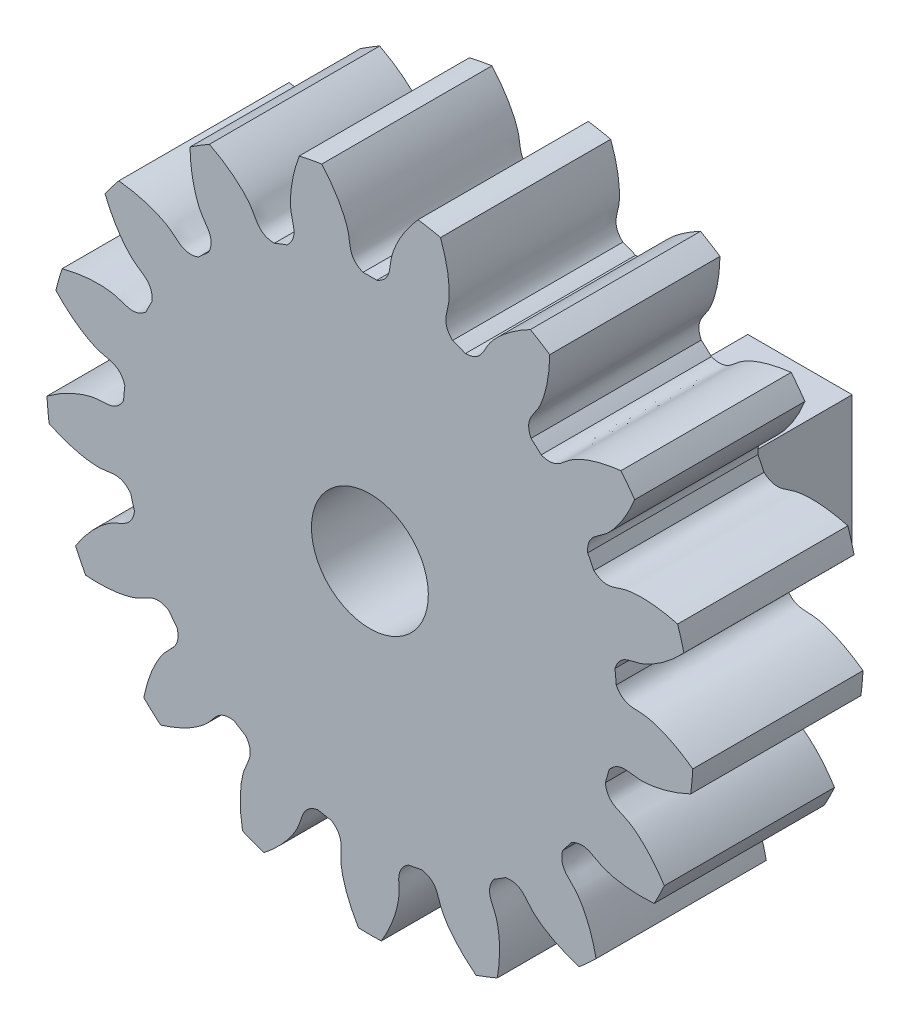
SolidWorks part; units mm, degrees
material "POM 乙缩醛共聚物"
ref_plane "前视基准面" through (0, 0, 0) normal (0, 0, 1) x (1, 0, 0)
ref_plane "上视基准面" through (0, 0, 0) normal (0, 1, 0) x (1, 0, 0)
ref_plane "右视基准面" through (0, 0, 0) normal (1, 0, 0) x (0, 0, -1)
sketch "草图1" plane through (0, 0, 0) normal (0, 0, 1) x (1, 0, 0)
  circle A0 centre (0, 0) radius 28.5
extrude "凸台-拉伸1" add sketch "草图1" along normal blind 15
ref_axis "基准轴1" through (0, 0, -0.75) along (0, 0, 1)
sketch "草图2" plane through (0, 0, 0) normal (0, 0, 1) x (1, 0, 0)
  line L0 (0, 0) -> (0, 28.5) construction
  circle A0 centre (0, 0) radius 28.5 construction
  arc A1 (0.6051, 21.7416) -> (-0.6051, 21.7416) centre (0, 0) ccw
  arc A2 (9.3469, 32.2222) -> (-9.3469, 32.2222) centre (0, 0) ccw
  spline S0 degree 3 poles (0.6051, 21.7416) (1.8836, 22.2745) (1.6986, 23.2644) (1.9149, 24.1945) (1.9349, 24.2735) (1.9591, 24.3613) (1.9877, 24.4578) (2.0211, 24.5628) (2.0597, 24.6762) (2.1038, 24.7979) (2.1538, 24.9276) (2.21, 25.0651) (2.2727, 25.2103) (2.3424, 25.3629) (2.4192, 25.5227) (2.5035, 25.6895) (2.5956, 25.8631) (2.6958, 26.0432) (2.8044, 26.2295) (2.9217, 26.4218) (3.048, 26.6198) (3.1836, 26.8232) (3.3286, 27.0317) (3.4835, 27.245) (3.6483, 27.4629) (3.8234, 27.6849) (4.009, 27.9108) (4.2053, 28.1402) (4.4126, 28.3728) (4.6309, 28.6082) (4.8606, 28.8462) (5.1018, 29.0862) (5.3546, 29.328) (5.6193, 29.5712) (5.896, 29.8154) (6.1849, 30.0602) (6.486, 30.3052) (6.7995, 30.55) (7.1255, 30.7943) (7.4641, 31.0376) (7.8154, 31.2795) (8.1795, 31.5197) (8.6875, 31.8403) (9.0797, 32.0716) (9.3469, 32.2222) knots 0 0 0 0 0.193883 0.199024 0.204851 0.211363 0.21856 0.226443 0.235011 0.244265 0.254205 0.264829 0.27614 0.288136 0.300817 0.314184 0.328236 0.342973 0.358397 0.374505 0.391299 0.408779 0.426944 0.445795 0.465331 0.485552 0.506459 0.528051 0.550329 0.573293 0.596941 0.621276 0.646296 0.672001 0.698392 0.725468 0.753229 0.781677 0.810809 0.840627 0.871131 0.90232 0.934195 1 1 1 1
  spline S1 degree 3 poles (-0.6051, 21.7416) (-1.8836, 22.2745) (-1.6986, 23.2644) (-1.9149, 24.1945) (-1.9349, 24.2735) (-1.9591, 24.3613) (-1.9877, 24.4578) (-2.0211, 24.5628) (-2.0597, 24.6762) (-2.1038, 24.7979) (-2.1538, 24.9276) (-2.21, 25.0651) (-2.2727, 25.2103) (-2.3424, 25.3629) (-2.4192, 25.5227) (-2.5035, 25.6895) (-2.5956, 25.8631) (-2.6958, 26.0432) (-2.8044, 26.2295) (-2.9217, 26.4218) (-3.048, 26.6198) (-3.1836, 26.8232) (-3.3286, 27.0317) (-3.4835, 27.245) (-3.6483, 27.4629) (-3.8234, 27.6849) (-4.009, 27.9108) (-4.2053, 28.1402) (-4.4126, 28.3728) (-4.6309, 28.6082) (-4.8606, 28.8462) (-5.1018, 29.0862) (-5.3546, 29.328) (-5.6193, 29.5712) (-5.896, 29.8154) (-6.1849, 30.0602) (-6.486, 30.3052) (-6.7995, 30.55) (-7.1255, 30.7943) (-7.4641, 31.0376) (-7.8154, 31.2795) (-8.1795, 31.5197) (-8.6875, 31.8403) (-9.0797, 32.0716) (-9.3469, 32.2222) knots 0 0 0 0 0.193883 0.199024 0.204851 0.211363 0.21856 0.226443 0.235011 0.244265 0.254205 0.264829 0.27614 0.288136 0.300817 0.314184 0.328236 0.342973 0.358397 0.374505 0.391299 0.408779 0.426944 0.445795 0.465331 0.485552 0.506459 0.528051 0.550329 0.573293 0.596941 0.621276 0.646296 0.672001 0.698392 0.725468 0.753229 0.781677 0.810809 0.840627 0.871131 0.90232 0.934195 1 1 1 1
extrude "切除-拉伸1" cut sketch "草图2" along normal through all
pattern_circular "阵列(圆周)1" count 17 every 21.176 about axis through (0, 0, -0.75) along (0, 0, 1) of "切除-拉伸1"
sketch "草图3" plane through (0, 0, 0) normal (0, 0, 1) x (1, 0, 0)
  circle A0 centre (0, 0) radius 25.5 construction
  dimension "Dn" = 51
sketch "草图4" plane through (0, 0, 0) normal (0, 0, -1) x (-1, 0, 0)
  line L0 (-12.5, 3.9538) -> (-3.3, 3.9538)
  line L1 (3.3, 3.9538) -> (12.5, 3.9538)
  line L2 (12.5, 3.9538) -> (12.5, -8.0462)
  line L3 (12.5, -8.0462) -> (-12.5, -8.0462)
  line L4 (-12.5, -8.0462) -> (-12.5, 3.9538)
  circle A0 centre (0, 0) radius 5.15
  dimension "D2" = 10.3
  dimension "D1" = 6.6
  dimension "D3" = 12
  dimension "D4" = 25
extrude "凸台-拉伸2" add sketch "草图4" along normal blind 15 contours A0 L0 L4 L3 L2 L1 region at (7.9, 3.6765, 0)
sketch "草图5" plane through (0, 3.9538, 0) normal (0, 1, 0) x (1, 0, 0)
  line L0 (-8.5, 15) -> (-8.5, 3) construction
  line L1 (-3.3, 15) -> (-12.5, 15) construction
  line L3 (-8.5, 3) -> (8.5, 15) construction
  line L4 (12.5, 15) -> (3.3, 15) construction
  line L5 (8.5, 15) -> (8.5, 3) construction
  line L7 (8.5, 3) -> (-8.5, 15) construction
  line L8 (-12.5, 15) -> (-12.5, 0) construction
  line L9 (12.5, 15) -> (12.5, 0) construction
  line L10 (-8.4182, 0) -> (-14.1376, 0) construction
  line L11 (-3.3, 0) -> (-12.5, 0) construction
  circle A0 centre (8.5, 11) radius 1.15
  circle A1 centre (8.5, 4) radius 1.15
  circle A2 centre (0, 9) radius 1.65
  circle A3 centre (-8.5, 11) radius 1.15
  circle A4 centre (-8.5, 4) radius 1.15
  dimension "D3" = 2.3
  dimension "D4" = 4
  dimension "D5" = 4
  dimension "D6" = 3.3
  dimension "D1" = 4
  dimension "D2" = 4
  dimension "D7" = 3
extrude "切除-拉伸2" cut sketch "草图5" against normal through all
sketch "草图6" plane through (0, 0, -15) normal (0, 0, -1) x (-1, 0, 0)
  circle A0 centre (0, 0) radius 5.15
extrude "切除-拉伸3" cut sketch "草图6" against normal through all
